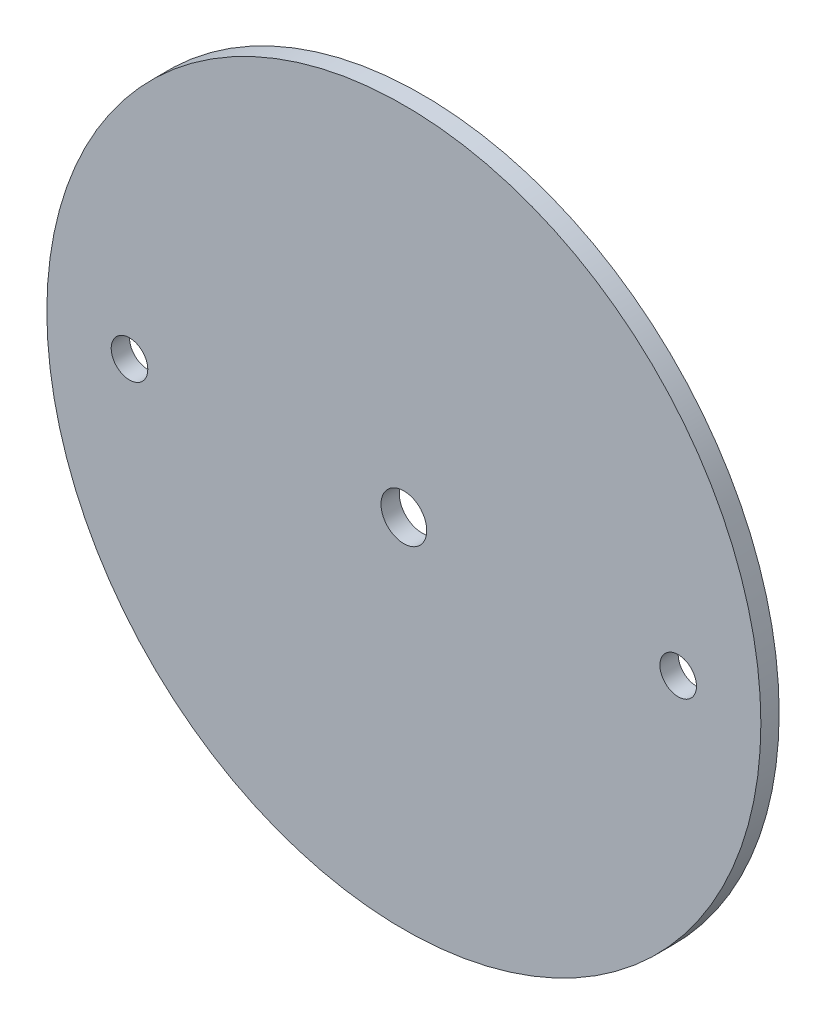
SolidWorks part; units mm, degrees
ref_plane "Front Plane" through (0, 0, 0) normal (0, 0, 1) x (1, 0, 0)
ref_plane "Top Plane" through (0, 0, 0) normal (0, 1, 0) x (1, 0, 0)
ref_plane "Right Plane" through (0, 0, 0) normal (1, 0, 0) x (0, 0, -1)
sketch "Sketch1" plane through (0, 0, 0) normal (0, 0, 1) x (1, 0, 0)
  circle A0 centre (0, 0) radius 61.976
  dimension "D1" = 123.952
extrude "Boss-Extrude1" add sketch "Sketch1" along normal mid plane 3.175
sketch "Sketch2" plane through (0, 0, 1.5875) normal (0, 0, 1) x (1, 0, 0)
  line L0 (-1000, 0) -> (49000, 0) construction
  line L1 (0, -1000) -> (0, 49000) construction
  point P4 (47.625, 0)
  point P5 (-47.625, 0)
  dimension "D2" = 95.25
  dimension "D1" = 47.625
hole_wizard "1/4 (0.25) Diameter Hole1" positions "Sketch2" profile "Sketch3" hole size "1/4" standard "ANSI Inch" end condition through all
sketch "Sketch3" plane through (-47.625, 0, 1.5875) normal (1, 0, 0) x (0, -1, 0)
  line L0 (0, 0) -> (0, 3.175)
  line L1 (0, 3.175) -> (3.175, 3.175)
  line L2 (3.175, 3.175) -> (3.175, 0)
  line L5 (3.175, 0) -> (0, 0)
  line L11 (0, -6.35) -> (0, 107.95) construction
  dimension "Thru Hole Dia." = 6.35
  dimension "Thru Hole Depth" = 3.175
sketch "Sketch4" plane through (0, 0, 1.5875) normal (0, 0, 1) x (1, 0, 0)
  point P0 (0, 0)
hole_wizard "5/16 (0.3125) Diameter Hole1" positions "Sketch4" profile "Sketch5" hole size "5/16" standard "ANSI Inch"
sketch "Sketch5" plane through (0, 0, 1.5875) normal (1, 0, 0) x (0, -1, 0)
  line L0 (0, 0) -> (0, 3.302)
  line L1 (0, 3.302) -> (3.9687, 3.302)
  line L2 (3.9687, 3.302) -> (3.9688, 0)
  line L5 (3.9688, 0) -> (0, 0)
  line L10 (0, 3.302) -> (-3.9688, 3.302) construction
  line L11 (0, -6.35) -> (0, 107.95) construction
  dimension "Hole Dia." = 7.9375
  dimension "Hole Depth" = 3.302
  dimension "Drill Angle" = 180
equation "\"AIRFRAME_OD\"= 5.15in"
equation "\"AIRFRAME_ID\"= 5.00in"
equation "\"FLAT_T\"= 0.125in"
equation "\"NOSE_EXP_L\"= 27in"
equation "\"NOSE_SHOULDER_L\"= 5in"
equation "\"MAIN_L\"= 30in"
equation "\"RECO_COUP_L\"= 10in"
equation "\"RECO_SWITCH_L\"= 2in"
equation "\"DROGUE_L\"= 20in"
equation "\"ATS_FORE_COUP_L\"= 5.5in"
equation "\"ATS_AFT_COUP_L\"= 4.5in"
equation "\"LOWER_L\"= 30in"
equation "\"FIN_N\"= 4"
equation "\"CR_AFT_X\"= 0.5in"
equation "\"CR_FORE_X\"= 9.25in"
equation "\"FIN_ROOT\"= 8in"
equation "\"FIN_X\"= 0.75in"
equation "\"MOTOR_OD\"= 3.091in"
equation "\"MOTOR_ID\"= 3.00in"
equation "\"COUPLER_OD\"= 4.998in"
equation "\"COUPLER_ID\"= 4.88in"
equation "\"D1@Sketch1\"=\"COUPLER_ID\""
equation "\"D1@Boss-Extrude1\"=\"FLAT_T\""
equation "\"RECO_ROD_X\"= 3.5in"
equation "\"ATS_ROD_X\"= 3.75in"
equation "\"D2@Sketch2\"=\"ATS_ROD_X\""
equation "\"MOTOR_L\"= 14in"
equation "\"MOTOR_LOWER_X\"= 2in"
equation "\"D1@Sketch2\"=\"ATS_ROD_X\"/2"
